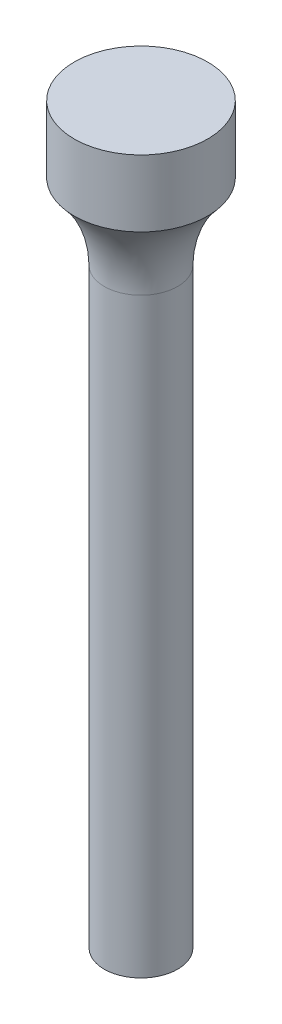
SolidWorks part; units mm, degrees
ref_plane "Front" through (0, 0, 0) normal (0, 0, 1) x (1, 0, 0)
ref_plane "Top" through (0, 0, 0) normal (0, 1, 0) x (1, 0, 0)
ref_plane "Right" through (0, 0, 0) normal (1, 0, 0) x (0, 0, -1)
sketch "Sketch1" plane through (0, 0, 0) normal (0, 1, 0) x (1, 0, 0)
  circle A0 centre (0, 0) radius 1.65
  dimension "D1" = 3.3
extrude "Boss-Extrude1" add sketch "Sketch1" along normal blind 30
sketch "Sketch2" plane through (0, 30, 0) normal (0, 1, 0) x (1, 0, 0)
  circle A0 centre (0, 0) radius 3
  point P3 (0, 0)
  dimension "D1" = 6
extrude "Boss-Extrude2" add sketch "Sketch2" along normal blind 3
fillet "Fillet1" radius 5 1 edges at (0, 30, 1.65)
